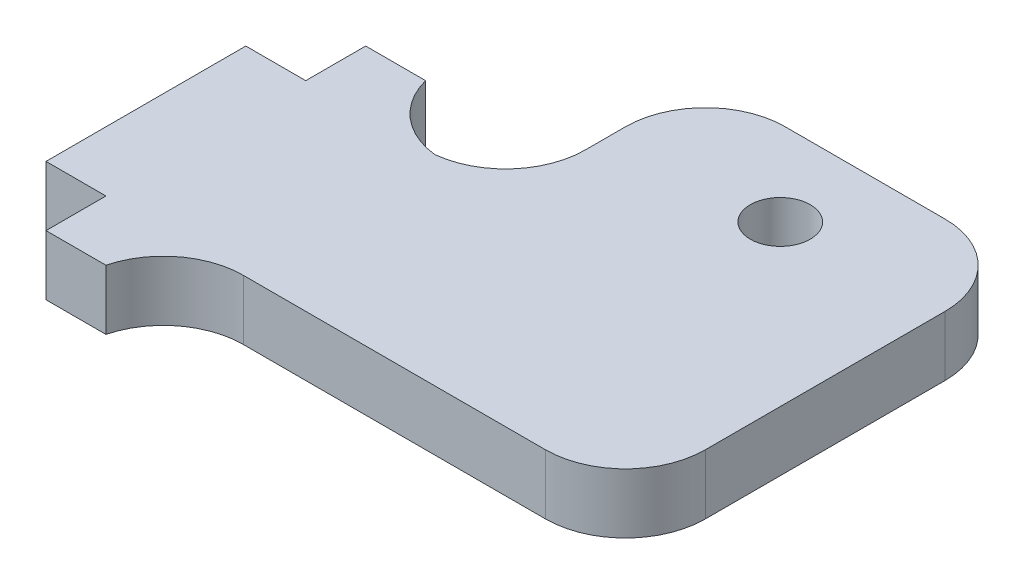
SolidWorks part; units mm, degrees
ref_plane "Front Plane" through (0, 0, 0) normal (0, 0, 1) x (1, 0, 0)
ref_plane "Top Plane" through (0, 0, 0) normal (0, 1, 0) x (1, 0, 0)
ref_plane "Right Plane" through (0, 0, 0) normal (1, 0, 0) x (0, 0, -1)
sketch "Sketch1" plane through (0, 0, 0) normal (0, 1, 0) x (1, 0, 0)
  line L1 (-14.5, 10) -> (14.5, 10)
  line L2 (-14.5, 10) -> (-14.5, -10)
  line L3 (-14.5, -10) -> (14.5, -10)
  line L4 (14.5, 10) -> (14.5, -10)
  line L5 (-14.5, 10) -> (14.5, -10) construction
  line L6 (-14.5, -10) -> (14.5, 10) construction
  line L7 (-14.5, 10) -> (-1.5, 10)
  line L8 (-14.5, 10) -> (-14.5, 0)
  line L9 (-14.5, 0) -> (-1.5, 0)
  line L10 (-1.5, 10) -> (-1.5, 0)
  line L11 (-14.5, 10) -> (-1.5, 0) construction
  line L12 (-14.5, 0) -> (-1.5, 10) construction
  line L13 (-11.5, -10) -> (-8.5, -10)
  line L14 (-11.5, -10) -> (-11.5, -13)
  line L15 (-11.5, -13) -> (-8.5, -13)
  line L16 (-8.5, -10) -> (-8.5, -13)
  line L17 (-11.5, -10) -> (-8.5, -13) construction
  line L18 (-11.5, -13) -> (-8.5, -10) construction
  line L19 (-11.5, 3) -> (-8.5, 3)
  line L20 (-11.5, 3) -> (-11.5, 0)
  line L21 (-11.5, 0) -> (-8.5, 0)
  line L22 (-8.5, 3) -> (-8.5, 0)
  line L23 (-11.5, 3) -> (-8.5, 0) construction
  line L24 (-11.5, 0) -> (-8.5, 3) construction
  circle A0 centre (6.5, 5.75) radius 1.5
  point P0 (0, 0)
  point P5 (-10, -11.5)
  point P7 (-8, 5)
  point P17 (-10, 1.5)
  point P22 (0, 0)
  dimension "D5" = 3
  dimension "D1" = 29
  dimension "D2" = 20
  dimension "D3" = 13
  dimension "D4" = 10
  dimension "D6" = 15.75
  dimension "D7" = 8
  dimension "D8" = 3
  dimension "D9" = 3
  dimension "D10" = 3
  dimension "D11" = 3
  dimension "D12" = 3
extrude "Boss-Extrude1" add sketch "Sketch1" along normal blind 3 contours L1 L10 L9 L2 L3 L4 A0 | L16 L3 L14 L15 | L19 L22 L21 L20
fillet "Fillet1" radius 4 6 edges at (-8.5, 1.5, 0) (-8.5, 1.5, 10) (14.5, 1.5, 10) (14.5, 1.5, -10) (-1.5, 1.5, -10) (-1.5, 1.5, 0)
